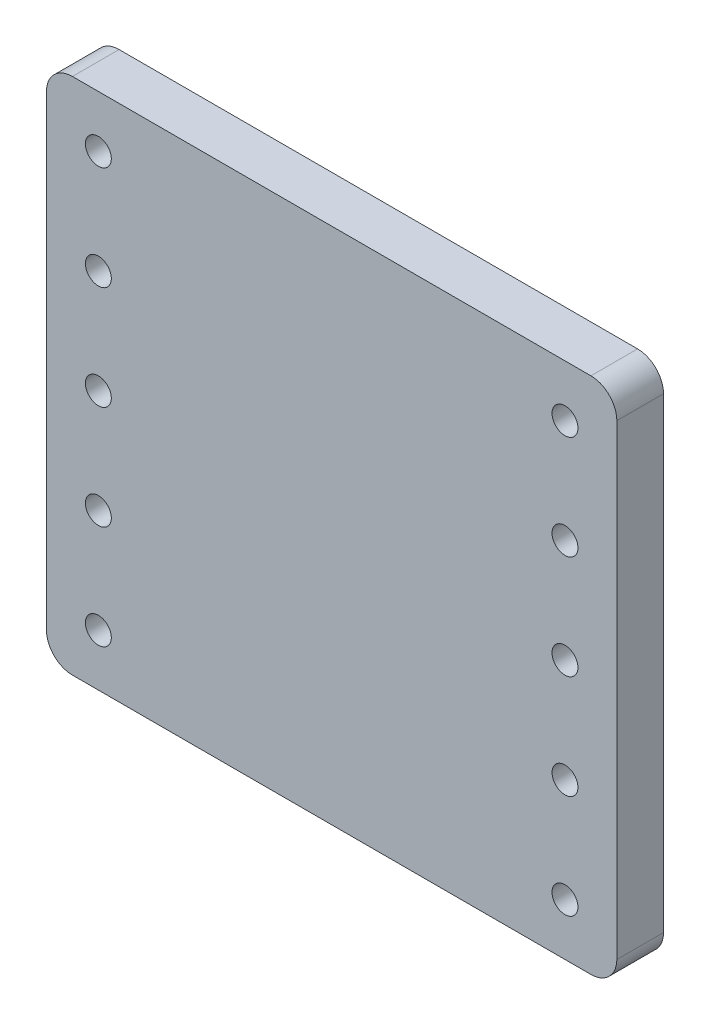
SolidWorks part; units mm, degrees
ref_plane "前视基准面" through (0, 0, 0) normal (0, 0, 1) x (1, 0, 0)
ref_plane "上视基准面" through (0, 0, 0) normal (0, 1, 0) x (1, 0, 0)
ref_plane "右视基准面" through (0, 0, 0) normal (1, 0, 0) x (0, 0, -1)
sketch "草图1" plane through (0, 0, 0) normal (0, 0, 1) x (1, 0, 0)
  line L0 (-90, -80) -> (-90, 80) construction
  line L1 (-100, -100) -> (100, -100)
  line L2 (-110, -90) -> (-110, 90)
  line L3 (-100, 100) -> (100, 100)
  line L4 (110, -90) -> (110, 90)
  line L5 (-110, -100) -> (110, 100) construction
  line L6 (-110, 100) -> (110, -100) construction
  line L7 (90, -80) -> (90, 80) construction
  line L8 (0, 0) -> (0, 49.5511) construction
  arc A0 (100, 100) -> (110, 90) centre (100, 90) cw
  arc A1 (100, -100) -> (110, -90) centre (100, -90) ccw
  arc A2 (-100, -100) -> (-110, -90) centre (-100, -90) cw
  arc A3 (-110, 90) -> (-100, 100) centre (-100, 90) cw
  circle A8 centre (-90, 0) radius 5
  circle A9 centre (90, 0) radius 5
  circle A10 centre (-90, 40) radius 5
  circle A11 centre (-90, -40) radius 5
  circle A12 centre (90, -40) radius 5
  circle A13 centre (90, 40) radius 5
  circle A14 centre (-90, -80) radius 5
  circle A15 centre (-90, 80) radius 5
  circle A16 centre (90, -80) radius 5
  circle A17 centre (90, 80) radius 5
  point P0 (0, 0)
  point P40 (0, 0)
  point P41 (0, 0)
  point P42 (-90, 0)
  point P43 (90, 0)
  point P44 (90, 0)
  point P45 (-90, -40)
  dimension "D2" = 10
  dimension "D3" = 10
  dimension "D4" = 20
  dimension "D5" = 20
  dimension "D6" = 10
  dimension "D8" = 10
  dimension "D9" = 10
  dimension "D10" = 10
  dimension "D11" = 10
  dimension "D12" = 40
  dimension "D13" = 40
  dimension "D16" = 40
  dimension "D17" = 40
  dimension "D1" = 200
  dimension "D7" = 220
  dimension "D14" = 20
  dimension "D15" = 20
extrude "凸台-拉伸1" add sketch "草图1" along normal mid plane 10
sketch "草图3" plane through (0, 0, -5) normal (0, 0, -1) x (-1, 0, 0)
  line L0 (110, 90) -> (110, -90) construction
  line L5 (100, -100) -> (-100, -100) construction
  line L6 (-110, -90) -> (-110, 90) construction
  line L7 (-100, 100) -> (100, 100) construction
  line L8 (110, 90) -> (110, -90)
  line L9 (100, -100) -> (-100, -100)
  line L10 (-110, -90) -> (-110, 90)
  line L11 (-100, 100) -> (100, 100)
  line L13 (-100, -90) -> (100, -90)
  line L14 (-100, -90) -> (-100, 90)
  line L15 (-100, 90) -> (100, 90)
  line L16 (100, -90) -> (100, 90)
  line L17 (-100, -90) -> (100, 90) construction
  line L18 (-100, 90) -> (100, -90) construction
  arc A0 (110, 90) -> (100, 100) centre (100, 90) ccw construction
  arc A1 (100, -100) -> (110, -90) centre (100, -90) ccw construction
  arc A2 (-110, -90) -> (-100, -100) centre (-100, -90) ccw construction
  arc A3 (-100, 100) -> (-110, 90) centre (-100, 90) ccw construction
  arc A4 (110, 90) -> (100, 100) centre (100, 90) ccw
  arc A5 (100, -100) -> (110, -90) centre (100, -90) ccw
  arc A6 (-110, -90) -> (-100, -100) centre (-100, -90) ccw
  arc A7 (-100, 100) -> (-110, 90) centre (-100, 90) ccw
  point P3 (0, 0)
extrude "凸台-拉伸2" add sketch "草图3" along normal blind 8
